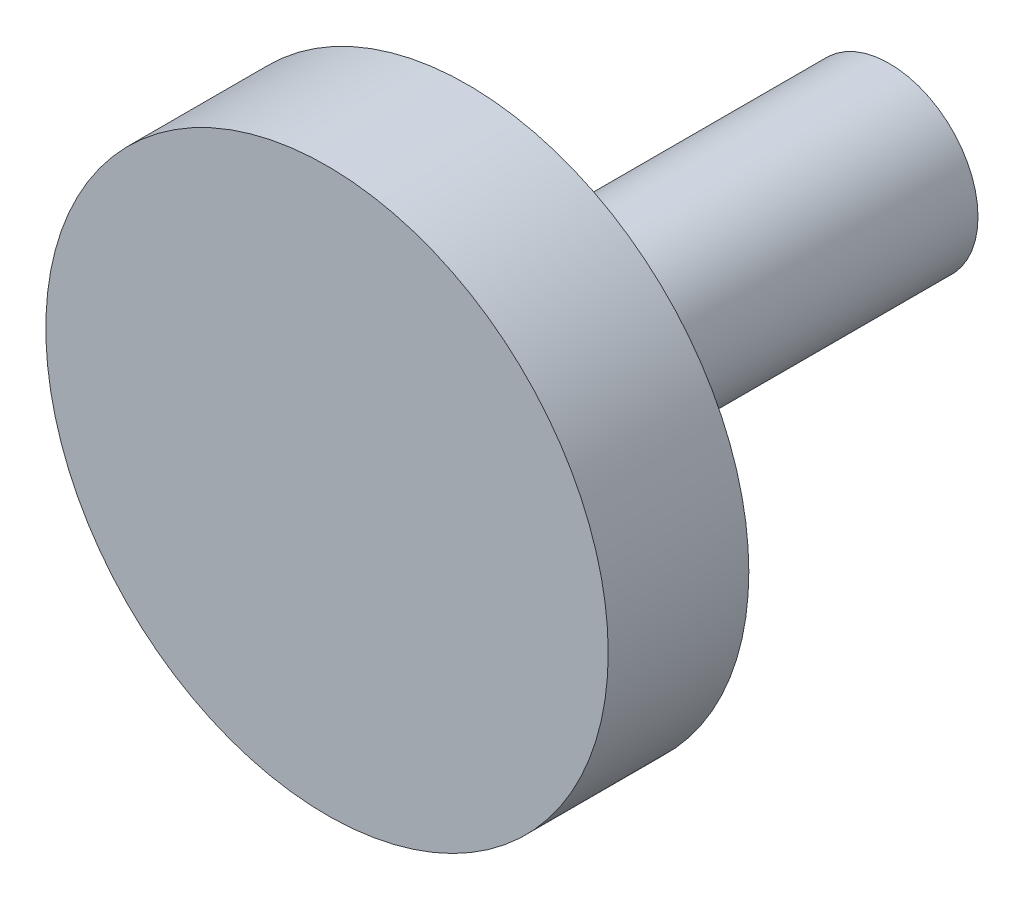
SolidWorks part; units mm, degrees
ref_plane "Front Plane" through (0, 0, 0) normal (0, 0, 1) x (1, 0, 0)
ref_plane "Top Plane" through (0, 0, 0) normal (0, 1, 0) x (1, 0, 0)
ref_plane "Right Plane" through (0, 0, 0) normal (1, 0, 0) x (0, 0, -1)
sketch "Sketch1" plane through (0, 0, 0) normal (0, 0, 1) x (1, 0, 0)
  circle A0 centre (0, 0) radius 12.7
  dimension "D1" = 25.4
extrude "Boss-Extrude1" add sketch "Sketch1" along normal blind 6.35
sketch "Sketch2" plane through (0, 0, 0) normal (0, 0, 1) x (1, 0, 0)
  circle A0 centre (0, 0) radius 4
  dimension "D1" = 8
extrude "Boss-Extrude2" add sketch "Sketch2" against normal blind 19.05
